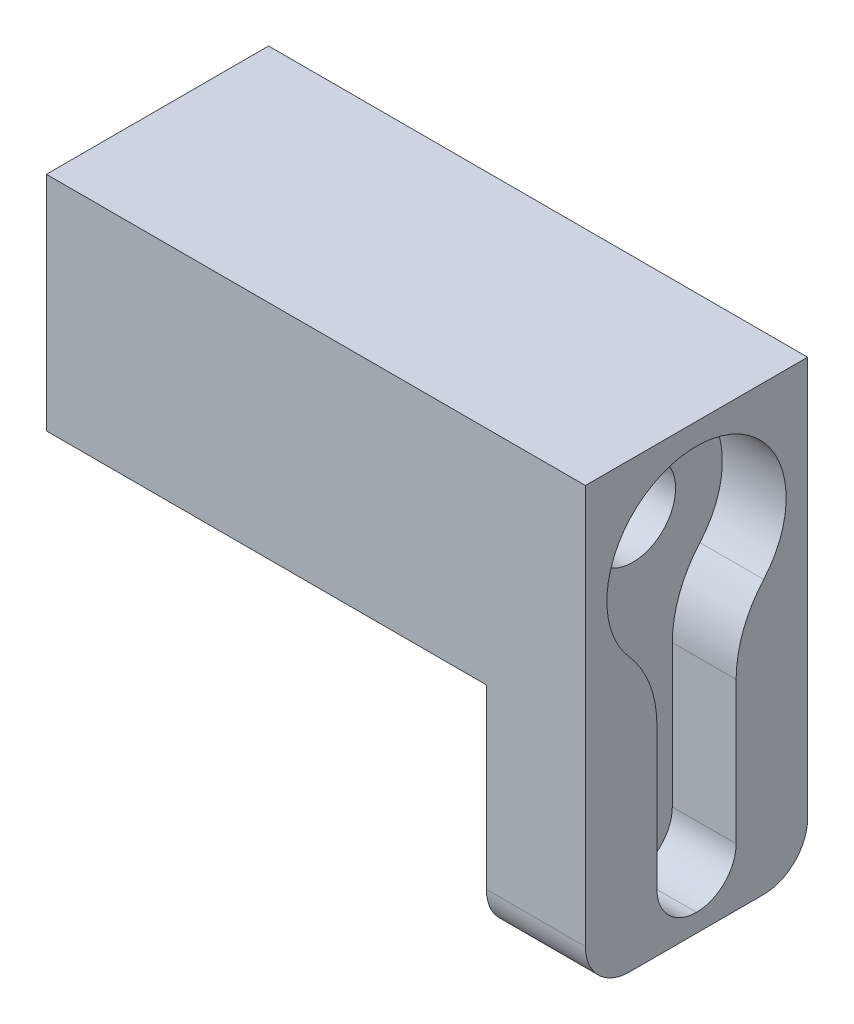
SolidWorks part; units mm, degrees
ref_plane "Front Plane" through (0, 0, 0) normal (0, 0, 1) x (1, 0, 0)
ref_plane "Top Plane" through (0, 0, 0) normal (0, 1, 0) x (1, 0, 0)
ref_plane "Right Plane" through (0, 0, 0) normal (1, 0, 0) x (0, 0, -1)
sketch "Sketch1" plane through (0, 0, 0) normal (1, 0, 0) x (0, 0, -1)
  line L1 (-10, 10) -> (10, 10)
  line L2 (-10, 10) -> (-10, -10)
  line L3 (-10, -10) -> (10, -10)
  line L4 (10, 10) -> (10, -10)
  line L5 (-10, 10) -> (10, -10) construction
  line L6 (-10, -10) -> (10, 10) construction
  point P0 (0, 0)
  dimension "D1" = 20
  dimension "D2" = 20
extrude "Boss-Extrude1" add sketch "Sketch1" along normal blind 20
sketch "Sketch2" plane through (20, 0, 0) normal (1, 0, 0) x (0, 0, -1)
  line L1 (-22.5, 35) -> (22.5, 35)
  line L2 (-22.5, 35) -> (-22.5, -35)
  line L3 (-22.5, -35) -> (22.5, -35)
  line L4 (22.5, 35) -> (22.5, -35)
  line L5 (-22.5, 35) -> (22.5, -35) construction
  line L6 (-22.5, -35) -> (22.5, 35) construction
  point P0 (0, 0)
  dimension "D1" = 45
  dimension "D2" = 70
extrude "Boss-Extrude2" add sketch "Sketch2" along normal blind 9
sketch "Sketch4" plane through (29, 0, 0) normal (1, 0, 0) x (0, 0, -1)
  line L0 (0, 7.65) -> (0, 8.1702) construction
  line L1 (7.65, 7.65) -> (-7.65, 7.65) construction
  line L17 (3.6, -26.55) -> (-3.6, -26.55) construction
  line L18 (-7.65, 7.65) -> (7.65, 7.65) construction
  line L22 (-7.65, 7.65) -> (-7.65, -27.55) construction
  line L23 (-7.65, -27.55) -> (7.65, -27.55) construction
  line L24 (7.65, 7.65) -> (7.65, -27.55) construction
  line L25 (-7.65, 7.65) -> (7.65, -27.55) construction
  line L26 (-7.65, -27.55) -> (7.65, 7.65) construction
  line L27 (3.6, -26.55) -> (3.6, -28.55) construction
  line L28 (3.6, -28.55) -> (-3.6, -28.55) construction
  line L29 (-3.6, -26.55) -> (-3.6, -28.55) construction
  line L30 (3.6, -26.55) -> (-3.6, -28.55) construction
  line L31 (3.6, -28.55) -> (-3.6, -26.55) construction
  line L34 (3.6, -28.55) -> (-3.6, -28.55)
  line L35 (-3.6, -28.55) -> (-3.6, -7.3118)
  line L36 (3.6, -28.55) -> (3.6, -7.3118)
  arc A1 (3.6, -6.75) -> (-3.6, -6.75) centre (0, 0) ccw construction
  arc A2 (3.6, -7.3118) -> (-3.6, -7.3118) centre (0, 0) ccw
  point P1 (0, -27.55)
  point P7 (0, -13.75)
  point P10 (0, 7.65)
  point P14 (0, -9.95)
  dimension "D1" = 15.3
  dimension "D5" = 2
  dimension "D2" = 15.3
  dimension "D3" = 35.2
  dimension "D4" = 7.2
extrude "Cut-Extrude1" cut sketch "Sketch4" against normal blind 5.8
fillet "Fillet1" radius 3.6 2 edges at (26.1, -28.55, 3.6) (26.1, -28.55, -3.6)
fillet "Fillet2" radius 10 2 edges at (26.1, -7.3118, 3.6) (26.1, -7.3118, -3.6)
sketch "Sketch5" plane through (0, 0, 0) normal (-1, 0, 0) x (0, 0, 1)
  circle A0 centre (0, 0) radius 3.9
  dimension "D1" = 7.8
extrude "Cut-Extrude2" cut sketch "Sketch5" against normal through all
sketch "Sketch6" plane through (23.2, 0, 0) normal (1, 0, 0) x (0, 0, -1)
  line L0 (0, -19.35) -> (0, 0) construction
  line L1 (0, -25.65) -> (0, -23.15) construction
  line L2 (0, -23.15) -> (0, -21.85) construction
  line L3 (0, -21.85) -> (0, -19.35) construction
  circle A0 centre (0, -20.6) radius 1.75
  dimension "D5" = 3.5
  dimension "D1" = 19.35
  dimension "D2" = 2.5
  dimension "D3" = 1.3
  dimension "D4" = 2.5
extrude "Cut-Extrude3" cut sketch "Sketch6" against normal up to next
sketch "Sketch7" plane through (0, -35, 0) normal (0, -1, 0) x (1, 0, 0)
  line L1 (29, 22.5) -> (20, 22.5)
  line L2 (29, 22.5) -> (29, -22.5)
  line L3 (29, -22.5) -> (20, -22.5)
  line L4 (20, 22.5) -> (20, -22.5)
  line L5 (29, 22.5) -> (20, -22.5) construction
  line L6 (29, -22.5) -> (20, 22.5) construction
  point P5 (24.5, 0)
extrude "Cut-Extrude4" cut sketch "Sketch7" against normal blind 4.8
sketch "Sketch9" plane through (0, 35, 0) normal (0, 1, 0) x (1, 0, 0)
  line L1 (29, 22.5) -> (20, 22.5)
  line L2 (29, 22.5) -> (29, -22.5)
  line L3 (29, -22.5) -> (20, -22.5)
  line L4 (20, 22.5) -> (20, -22.5)
  line L5 (29, 22.5) -> (20, -22.5) construction
  line L6 (29, -22.5) -> (20, 22.5) construction
  point P4 (24.5, 0)
extrude "Cut-Extrude5" cut sketch "Sketch9" against normal blind 23.8
sketch "Sketch10" plane through (20, 0, 0) normal (-1, 0, 0) x (0, 0, 1)
  line L0 (-22.5, 11.2) -> (22.5, 11.2) construction
  line L1 (-10, 11.2) -> (-22.5, 11.2)
  line L2 (-10, 11.2) -> (-10, -30.2)
  line L3 (-10, -30.2) -> (-22.5, -30.2)
  line L4 (-22.5, 11.2) -> (-22.5, -30.2)
  line L5 (-10, 11.2) -> (-22.5, -30.2) construction
  line L6 (-10, -30.2) -> (-22.5, 11.2) construction
  line L7 (22.5, -30.2) -> (-22.5, -30.2) construction
  line L9 (10, 11.2) -> (22.5, 11.2)
  line L10 (10, 11.2) -> (10, -30.2)
  line L11 (10, -30.2) -> (22.5, -30.2)
  line L12 (22.5, 11.2) -> (22.5, -30.2)
  line L13 (10, 11.2) -> (22.5, -30.2) construction
  line L14 (10, -30.2) -> (22.5, 11.2) construction
  point P4 (-16.25, -9.5)
  point P13 (16.25, -9.5)
extrude "Cut-Extrude6" cut sketch "Sketch10" against normal blind 23.8
sketch "Sketch11" plane through (20, 0, 0) normal (-1, 0, 0) x (0, 0, 1)
  line L5 (-10, 11.2) -> (10, 11.2)
  line L6 (-10, 11.2) -> (-10, 10)
  line L7 (-10, 10) -> (10, 10)
  line L8 (10, 11.2) -> (10, 10)
  line L9 (-10, 11.2) -> (10, 10) construction
  line L10 (-10, 10) -> (10, 11.2) construction
  point P4 (0, 10.6)
extrude "Cut-Extrude7" cut sketch "Sketch11" against normal blind 23.8
sketch "Sketch12" plane through (0, 0, 0) normal (-1, 0, 0) x (0, 0, 1)
  line L1 (10, 10) -> (-10, 10)
  line L2 (10, 10) -> (10, -10)
  line L3 (10, -10) -> (-10, -10)
  line L4 (-10, 10) -> (-10, -10)
  line L5 (10, 10) -> (-10, -10) construction
  line L6 (10, -10) -> (-10, 10) construction
  circle A0 centre (0, 0) radius 3.9
  point P4 (0, 0)
extrude "Boss-Extrude3" add sketch "Sketch12" along normal blind 20
sketch "Sketch13" plane through (-20, 0, 0) normal (-1, 0, 0) x (0, 0, 1)
  line L8 (10.1, -10.1) -> (10.1, 10.1)
  line L9 (10.1, 10.1) -> (-10.1, 10.1)
  line L10 (-10.1, 10.1) -> (-10.1, -10.1)
  line L11 (-10.1, -10.1) -> (10.1, -10.1)
  line L12 (10.1, -10.1) -> (10.1, 10.1)
  line L13 (10.1, 10.1) -> (-10.1, 10.1)
  line L14 (-10.1, 10.1) -> (-10.1, -10.1)
  line L15 (-10.1, -10.1) -> (10.1, -10.1)
  circle A0 centre (0, 0) radius 3.9
  dimension "D1" = 0.1
extrude "Boss-Extrude4" add sketch "Sketch13" against normal up to surface (40 mm away) up to face at (20, -20.6, -1.75)
sketch "Sketch14" plane through (0, 10, 0) normal (0, 1, 0) x (1, 0, 0)
  line L1 (29, 10) -> (20, 10)
  line L2 (29, 10) -> (29, -10)
  line L3 (29, -10) -> (20, -10)
  line L4 (20, 10) -> (20, -10)
  line L5 (29, 10) -> (20, -10) construction
  line L6 (29, -10) -> (20, 10) construction
  point P4 (24.5, 0)
extrude "Boss-Extrude5" add sketch "Sketch14" along normal blind 0.1
sketch "Sketch15" plane through (0, 0, 10) normal (0, 0, 1) x (1, 0, 0)
  line L1 (29, 10.1) -> (20, 10.1)
  line L2 (29, 10.1) -> (29, -30.2)
  line L3 (29, -30.2) -> (20, -30.2)
  line L4 (20, 10.1) -> (20, -30.2)
  line L5 (29, 10.1) -> (20, -30.2) construction
  line L6 (29, -30.2) -> (20, 10.1) construction
  point P4 (24.5, -10.05)
extrude "Boss-Extrude6" add sketch "Sketch15" along normal blind 0.1
sketch "Sketch16" plane through (0, 0, -10) normal (0, 0, -1) x (-1, 0, 0)
  line L1 (-29, -30.2) -> (-20, -30.2)
  line L2 (-29, -30.2) -> (-29, 10.1)
  line L3 (-29, 10.1) -> (-20, 10.1)
  line L4 (-20, -30.2) -> (-20, 10.1)
  line L5 (-29, -30.2) -> (-20, 10.1) construction
  line L6 (-29, 10.1) -> (-20, -30.2) construction
  point P4 (-24.5, -10.05)
extrude "Boss-Extrude7" add sketch "Sketch16" along normal blind 0.1
sketch "Sketch17" plane through (-20, 0, 0) normal (-1, 0, 0) x (0, 0, 1)
  circle A0 centre (0, 0) radius 4.8309
extrude "Boss-Extrude8" add sketch "Sketch17" against normal blind 39
sketch "Sketch18" plane through (-20, 0, 0) normal (-1, 0, 0) x (0, 0, 1)
  circle A0 centre (0, 0) radius 3
  dimension "D1" = 6
extrude "Cut-Extrude8" cut sketch "Sketch18" against normal blind 2
fillet "Fillet3" radius 3.23 1 edges at (-18, 0, 3)
fillet "Fillet4" radius 4 2 edges at (24.5, -30.2, -10.1) (24.5, -30.2, 10.1)
